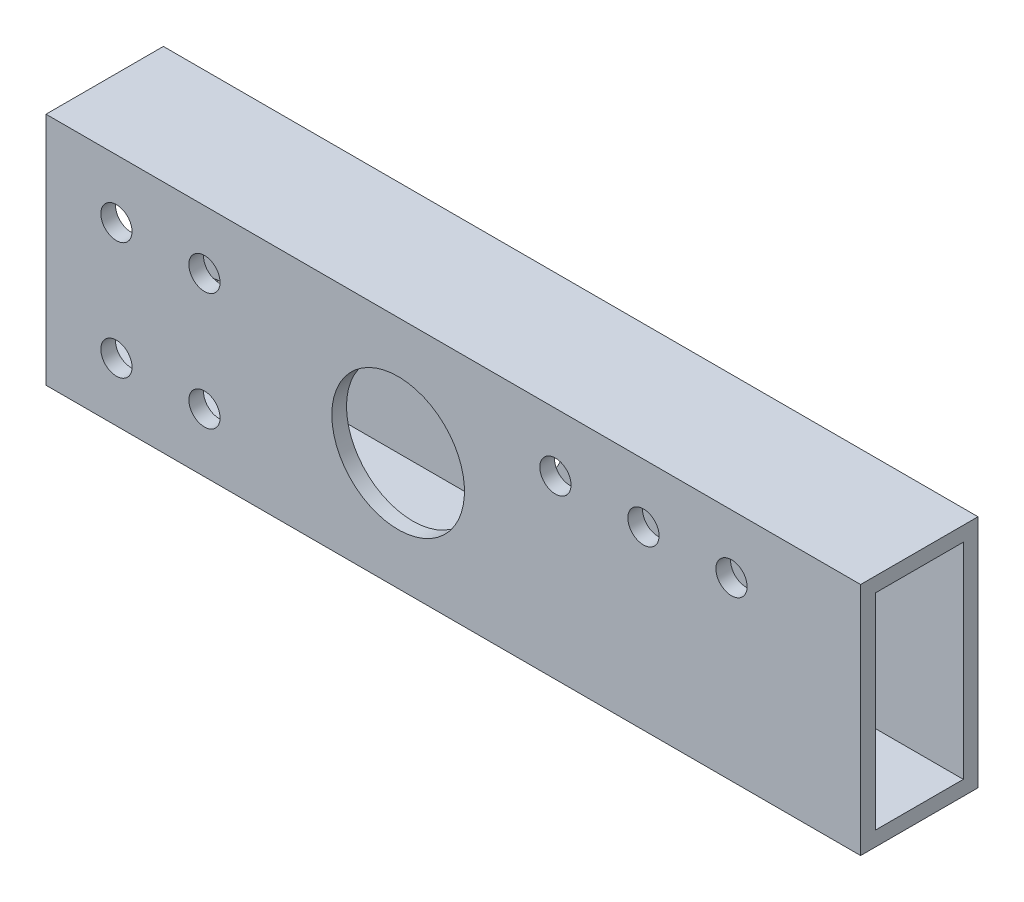
SolidWorks part; units mm, degrees
ref_plane "Front Plane" through (0, 0, 0) normal (0, 0, 1) x (1, 0, 0)
ref_plane "Top Plane" through (0, 0, 0) normal (0, 1, 0) x (1, 0, 0)
ref_plane "Right Plane" through (0, 0, 0) normal (1, 0, 0) x (0, 0, -1)
sketch "Sketch1" plane through (0, 0, 0) normal (0, 1, 0) x (1, 0, 0)
  line L1 (0, 0) -> (176.276, 0)
  line L2 (0, 0) -> (0, 25.4)
  line L3 (0, 25.4) -> (176.276, 25.4)
  line L4 (176.276, 0) -> (176.276, 25.4)
  dimension "D1" = 176.276
  dimension "D2" = 25.4
extrude "Boss-Extrude1" add sketch "Sketch1" along normal blind 50.8
sketch "Sketch2" plane through (176.276, 0, 0) normal (1, 0, 0) x (0, 0, -1)
  line L0 (3.175, 47.625) -> (3.175, 3.175)
  line L1 (0, 50.8) -> (25.4, 50.8)
  line L2 (0, 50.8) -> (0, 0)
  line L3 (0, 0) -> (25.4, 0)
  line L4 (25.4, 50.8) -> (25.4, 0)
  line L5 (3.175, 3.175) -> (22.225, 3.175)
  line L6 (22.225, 47.625) -> (22.225, 3.175)
  line L7 (3.175, 47.625) -> (22.225, 47.625)
  dimension "D1" = 3.175
extrude "Cut-Extrude1" cut sketch "Sketch2" against normal through all flip side to cut
sketch "Sketch3" plane through (0, 0, -25.4) normal (0, 0, -1) x (-1, 0, 0)
  line L1 (-176.276, 50.8) -> (0, 50.8) construction
  line L2 (0, 50.8) -> (0, 0) construction
  circle A0 centre (-76.2, 25.4) radius 14.351
  dimension "D1" = 28.702
  dimension "D4" = 76.2
  dimension "D3" = 25.4
extrude "Cut-Extrude2" cut sketch "Sketch3" against normal through all
sketch "Sketch4" plane through (0, 0, 0) normal (0, 0, 1) x (1, 0, 0)
  line L0 (176.276, 50.8) -> (176.276, 0) construction
  line L2 (0, 50.8) -> (176.276, 50.8) construction
  circle A0 centre (148.336, 38.1) radius 3.3782
  circle A1 centre (129.286, 38.1) radius 3.3782
  circle A2 centre (110.236, 38.1) radius 3.3782
  dimension "D1" = 6.7564
  dimension "D2" = 6.7564
  dimension "D3" = 6.7564
  dimension "D4" = 27.94
  dimension "D5" = 19.05
  dimension "D6" = 19.05
  dimension "D7" = 12.7
  dimension "D8" = 12.7
  dimension "D9" = 12.7
extrude "Cut-Extrude3" cut sketch "Sketch4" against normal through all
sketch "Sketch5" plane through (0, 0, 0) normal (0, 0, 1) x (1, 0, 0)
  line L0 (0, 50.8) -> (0, 0) construction
  line L1 (0, 0) -> (176.276, 0) construction
  line L2 (0, 50.8) -> (176.276, 50.8) construction
  circle A0 centre (15.24, 38.1) radius 3.3782
  circle A1 centre (15.24, 12.7) radius 3.3782
  circle A2 centre (34.29, 12.7) radius 3.3782
  circle A3 centre (34.29, 38.1) radius 3.3782
  dimension "D5" = 6.7564
  dimension "D6" = 6.7564
  dimension "D7" = 6.7564
  dimension "D8" = 6.7564
  dimension "D1" = 15.24
  dimension "D2" = 19.05
  dimension "D3" = 15.24
  dimension "D4" = 19.05
  dimension "D9" = 12.7
  dimension "D10" = 12.7
  dimension "D11" = 12.7
  dimension "D12" = 12.7
extrude "Cut-Extrude4" cut sketch "Sketch5" against normal through all
